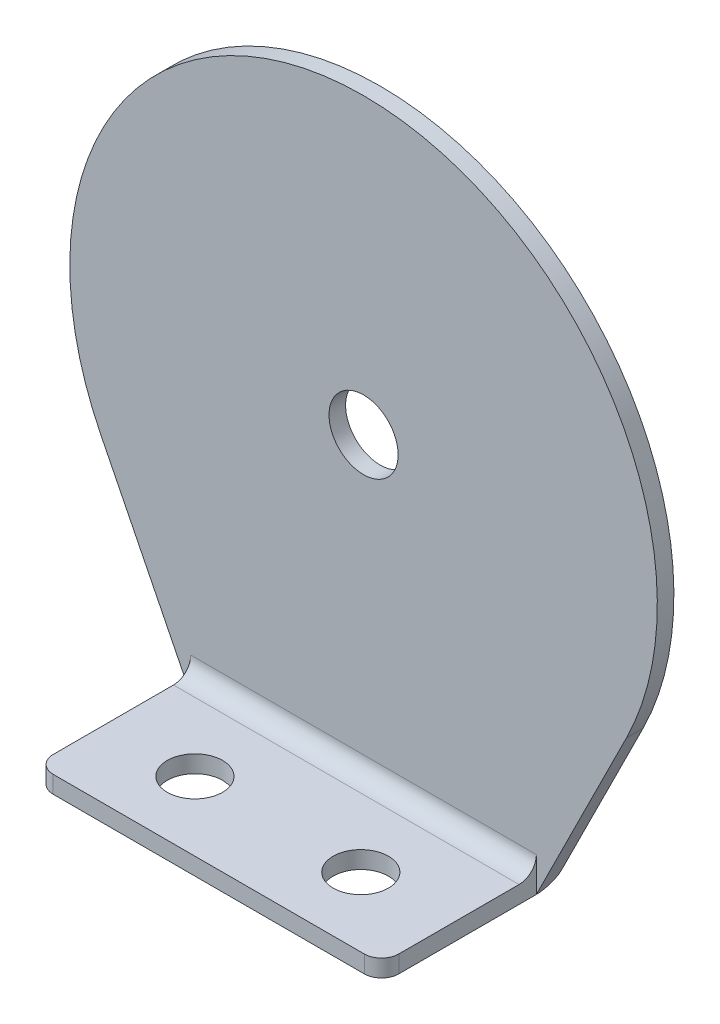
SolidWorks part; units mm, degrees
ref_plane "Front Plane" through (0, 0, 0) normal (0, 0, 1) x (1, 0, 0)
ref_plane "Top Plane" through (0, 0, 0) normal (0, 1, 0) x (1, 0, 0)
ref_plane "Right Plane" through (0, 0, 0) normal (1, 0, 0) x (0, 0, -1)
sketch "Sketch1" plane through (0, 0, 0) normal (0, 0, 1) x (1, 0, 0)
  line L0 (0, 0) -> (0, 55.626) construction
  line L1 (-24.1508, 16.5942) -> (-15.875, 0)
  line L2 (-15.875, 0) -> (15.875, 0)
  line L3 (24.1508, 16.5942) -> (15.875, 0)
  arc A0 (24.1508, 16.5942) -> (-24.1508, 16.5942) centre (0, 28.6385) ccw
  dimension "D2" = 26.9875
  dimension "D3" = 15.875
extrude "Boss-Extrude1" add sketch "Sketch1" along normal blind 1.524
sketch "Sketch2" plane through (0, 0, 1.524) normal (0, 0, 1) x (1, 0, 0)
  circle A0 centre (0, 28.6385) radius 3.175
  arc A1 (24.1508, 16.5942) -> (-24.1508, 16.5942) centre (0, 28.6385) ccw construction
  dimension "D1" = 6.35
extrude "Cut-Extrude1" cut sketch "Sketch2" against normal through all
sketch "Sketch3" plane through (0, 0, 1.524) normal (0, 0, 1) x (1, 0, 0)
  line L1 (-15.875, 0) -> (15.875, 0)
  line L2 (-15.875, 0) -> (-15.875, 1.5875)
  line L3 (-15.875, 1.5875) -> (15.875, 1.5875)
  line L4 (15.875, 0) -> (15.875, 1.5875)
  dimension "D1" = 1.5875
  dimension "D2" = 31.75
extrude "Boss-Extrude2" add sketch "Sketch3" along normal blind 14.224
fillet "Fillet1" radius 1.5875 4 edges at (0, 1.5875, 1.524) (0, 0, 0) (-15.875, 0.7937, 15.748) (15.875, 0.7937, 15.748)
sketch "Sketch4" plane through (0, 0, 0) normal (0, -1, 0) x (1, 0, 0)
  line L0 (0, 15.748) -> (0, 1.5875) construction
  line L1 (-14.2875, 15.748) -> (14.2875, 15.748) construction
  line L2 (-15.875, 1.5875) -> (15.875, 1.5875) construction
  circle A0 centre (7.62, 9.398) radius 2.54
  circle A1 centre (-7.62, 9.398) radius 2.54
  dimension "D1" = 5.08
  dimension "D2" = 6.35
  dimension "D3" = 7.62
extrude "Cut-Extrude2" cut sketch "Sketch4" against normal through all
